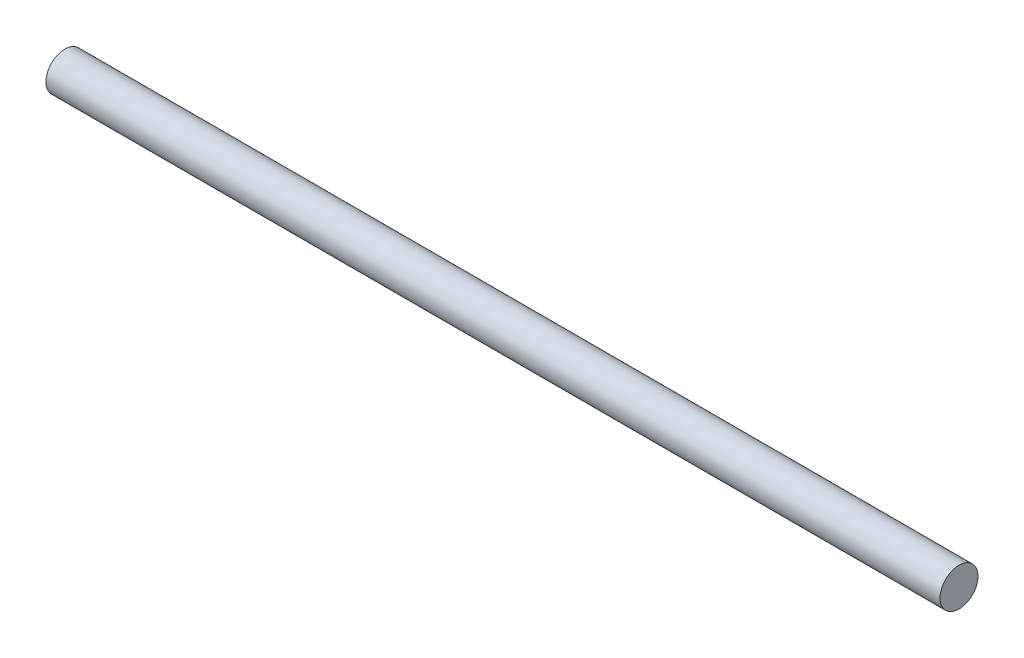
SolidWorks part; units mm, degrees
material "PVC 0.007 Plasticized"
ref_plane "Front Plane" through (0, 0, 0) normal (0, 0, 1) x (1, 0, 0)
ref_plane "Top Plane" through (0, 0, 0) normal (0, 1, 0) x (1, 0, 0)
ref_plane "Right Plane" through (0, 0, 0) normal (1, 0, 0) x (0, 0, -1)
ref_axis "X-axis" through (-88.99, 0, 0) along (1, 0, 0)
ref_axis "Y-axis" through (0, 55, 0) along (0, -1, 0)
ref_axis "Z-axis" through (0, 0, -88.99) along (0, 0, 1)
sketch "Sketch1" plane through (0, 0, 0) normal (1, 0, 0) x (0, 0, -1)
  circle A0 centre (0, 0) radius 1.7526
  dimension "D1" = 3.5052
extrude "Boss-Extrude1" add sketch "Sketch1" along normal mid plane 82.55
